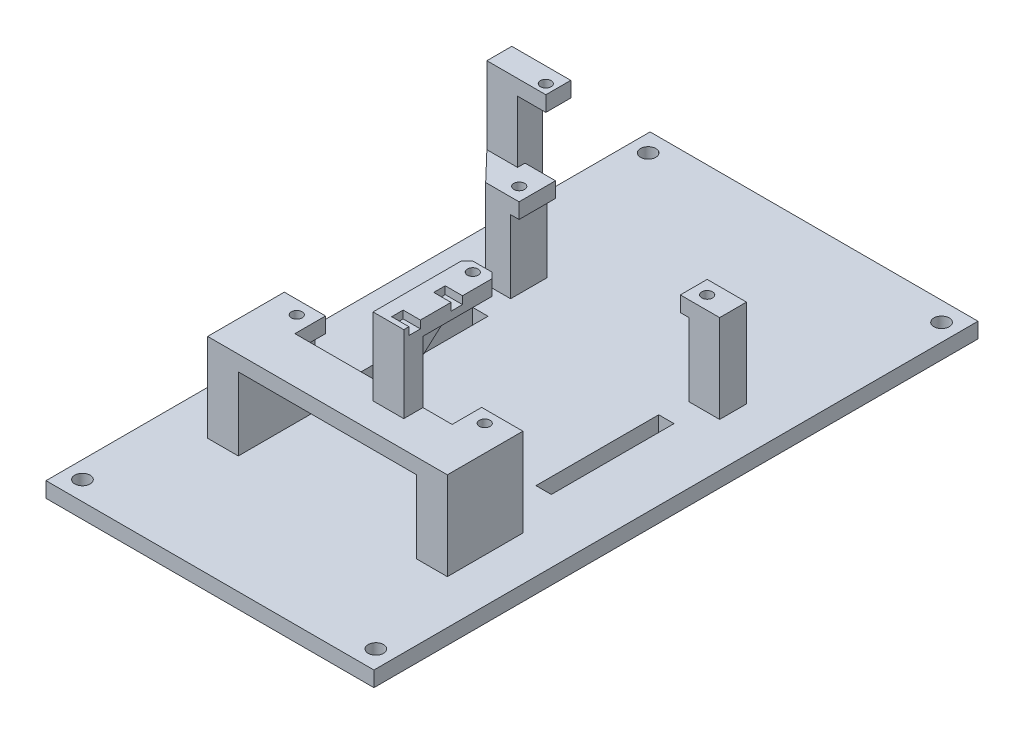
SolidWorks part; units mm, degrees
ref_plane "Front Plane" through (0, 0, 0) normal (0, 0, 1) x (1, 0, 0)
ref_plane "Top Plane" through (0, 0, 0) normal (0, 1, 0) x (1, 0, 0)
ref_plane "Right Plane" through (0, 0, 0) normal (1, 0, 0) x (0, 0, -1)
sketch "Sketch1" plane through (0, 0, 0) normal (0, 1, 0) x (1, 0, 0)
  line L1 (-42.75, 78.75) -> (42.75, 78.75)
  line L2 (-42.75, 78.75) -> (-42.75, -78.75)
  line L3 (-42.75, -78.75) -> (42.75, -78.75)
  line L4 (42.75, 78.75) -> (42.75, -78.75)
  line L5 (-42.75, 78.75) -> (42.75, -78.75) construction
  line L6 (-42.75, -78.75) -> (42.75, 78.75) construction
  point P0 (0, 0)
  dimension "D1" = 157.5
  dimension "D2" = 85.5
extrude "Boss-Extrude1" add sketch "Sketch1" along normal blind 4
sketch "Sketch2" plane through (0, 4, 0) normal (0, 1, 0) x (1, 0, 0)
  line L0 (-42.75, -78.75) -> (42.75, -78.75) construction
  line L1 (42.75, -78.75) -> (42.75, 78.75) construction
  line L2 (0, 0) -> (50000, 0) construction
  line L3 (0, 0) -> (0, -50000) construction
  circle A0 centre (38.25, -73.75) radius 2
  circle A1 centre (38.25, 73.75) radius 2
  circle A2 centre (-38.25, -73.75) radius 2
  circle A3 centre (-38.25, 73.75) radius 2
  dimension "D1" = 4
  dimension "D2" = 5
  dimension "D3" = 4.5
extrude "Cut-Extrude1" cut sketch "Sketch2" against normal up to next
sketch "Sketch5" plane through (0, 4, 0) normal (0, 1, 0) x (1, 0, 0)
  line L0 (-24.5, 26.3886) -> (-24.5, -31.6114) construction
  line L1 (-24.5, -31.6114) -> (24.5, -31.6114) construction
  line L2 (24.5, -31.6114) -> (24.5, 26.3886) construction
  line L3 (24.5, 26.3886) -> (-24.5, 26.3886) construction
  line L4 (0, 49.8886) -> (0, -35.1114) construction
  line L5 (-22.25, 67.25) -> (22.25, 67.25) construction
  line L6 (-22.25, 67.25) -> (-22.25, -67.25) construction
  line L7 (-22.25, -67.25) -> (22.25, -67.25) construction
  line L8 (22.25, 67.25) -> (22.25, -67.25) construction
  line L9 (-22.25, 67.25) -> (22.25, -67.25) construction
  line L10 (-22.25, -67.25) -> (22.25, 67.25) construction
  line L11 (-28, 49.8886) -> (28, 49.8886) construction
  line L12 (-28, 49.8886) -> (-28, -35.1114) construction
  line L13 (-28, -35.1114) -> (28, -35.1114) construction
  line L14 (28, 49.8886) -> (28, -35.1114) construction
  line L15 (24.5, 26.3886) -> (23.25, 26.3886) construction
  line L16 (-37, 36.9499) -> (-29, 36.9499)
  line L18 (-29.75, 22.8886) -> (-23.25, 22.8886)
  line L19 (-23.25, 32.3886) -> (-23.25, 22.8886)
  line L20 (23.25, 29.8886) -> (31.25, 29.8886)
  line L21 (23.25, 29.8886) -> (23.25, 22.8886)
  line L22 (23.25, 22.8886) -> (31.25, 22.8886)
  line L23 (31.25, 29.8886) -> (31.25, 22.8886)
  line L24 (-23.25, -48.1114) -> (23.25, -48.1114) construction
  line L25 (-31.25, -28.1114) -> (-23.25, -28.1114)
  line L26 (-31.25, -28.1114) -> (-31.25, -48.1114)
  line L27 (-31.25, -48.1114) -> (-23.25, -48.1114)
  line L28 (-23.25, -28.1114) -> (-23.25, -48.1114)
  line L29 (23.25, -28.4114) -> (31.25, -28.4114)
  line L30 (23.25, -28.4114) -> (23.25, -48.1114)
  line L31 (23.25, -48.1114) -> (31.25, -48.1114)
  line L32 (31.25, -28.4114) -> (31.25, -48.1114)
  line L33 (22.25, -16) -> (26.25, -16)
  line L34 (-22.25, -16) -> (-26.25, -16)
  line L35 (-22.25, -16) -> (-22.25, 16)
  line L36 (-22.25, 16) -> (-26.25, 16)
  line L37 (-26.25, -16) -> (-26.25, 16)
  line L38 (22.25, -16) -> (22.25, 16)
  line L39 (26.25, -16) -> (26.25, 16)
  line L40 (22.25, 16) -> (26.25, 16)
  line L41 (-23.25, 32.3886) -> (-29, 32.3886)
  line L42 (-29, 32.3886) -> (-29, 36.9499)
  line L43 (-37, 36.9499) -> (-37, 30.4499)
  line L44 (-37, 30.4499) -> (-29.75, 22.8886)
  circle A0 centre (-24.5, 26.3886) radius 1.4
  circle A1 centre (-24.13, 32.9499) radius 1.4
  circle A2 centre (8.89, -19.1201) radius 1.4
  circle A3 centre (24.5, -31.6114) radius 1.4
  circle A4 centre (24.5, 26.3886) radius 1.4
  circle A5 centre (-24.5, -31.6114) radius 1.4
  point P9 (0, 0)
  point P32 (23.25, 26.3886)
  point P46 (-22.25, 0)
  dimension "D1" = 24.5
  dimension "D2" = 26.3886
  dimension "D3" = 32.9499
  dimension "D4" = 24.13
  dimension "D5" = 2.8
  dimension "D6" = 33.02
  dimension "D7" = 52.07
  dimension "D8" = 49
  dimension "D9" = 58
  dimension "D18" = 4
  dimension "D21" = 3.5
  dimension "D24" = 3.5
  dimension "D10" = 44.5
  dimension "D11" = 134.5
  dimension "D12" = 56
  dimension "D13" = 85
  dimension "D14" = 28
  dimension "D15" = 3.5
  dimension "D16" = 1
  dimension "D17" = 3.5
  dimension "D19" = 6.5
  dimension "D20" = 1
  dimension "D22" = 8
  dimension "D23" = 1
  dimension "D25" = 1
  dimension "D26" = 3.2
  dimension "D27" = 8
  dimension "D28" = 8
  dimension "D29" = 20
  dimension "D30" = 32
  dimension "D31" = 4
  dimension "D32" = 6
  dimension "D33" = 1
  dimension "D34" = 8
  dimension "D35" = 6.5
extrude "Cut-Extrude3" cut sketch "Sketch5" against normal up to next contours L37 L34 L35 L36 | L39 L40 L38 L33 region at (-24.25, 4, 0)
extrude "Boss-Extrude3" add sketch "Sketch5<3>" along normal blind 23 contours L32 L29 L30 L31 | L28 L25 L26 L27 | L23 L20 L21 L22 | L43 L44 L18 L19 L41 L42 L16 | L28 A5 | L30 A3 | L21 A4 | L19 A0 | L41 A1 L19 region at (-30.3132, 4, -30.0503) region at (-24.2191, 4, -32.0291) region at (-24.5277, 4, -26.3886) region at (27.5785, 4, -26.3886) region at (24.5277, 4, -26.3886) region at (-27.3566, 4, 38.366) region at (-24.5277, 4, 31.6114) region at (27.3583, 4, 38.526) region at (24.5277, 4, 31.6114)
sketch "Sketch5<3>" plane through (0, 4, 0) normal (0, 1, 0) x (1, 0, 0) same geometry as "Sketch5"
sketch "Sketch6" plane through (-23.25, 0, 0) normal (1, 0, 0) x (0, 0, -1)
  line L0 (-28.1114, 27) -> (-28.1114, 4) construction
  line L1 (-48.1114, 27) -> (-28.1114, 27)
  line L2 (-48.1114, 27) -> (-48.1114, 23)
  line L3 (-48.1114, 23) -> (-28.1114, 23)
  line L4 (-28.1114, 27) -> (-28.1114, 23)
  line L5 (-28.1114, 4) -> (-48.1114, 4) construction
  dimension "D1" = 19
extrude "Boss-Extrude5" add sketch "Sketch6" along normal up to surface (46.5 mm away) up to face at (23.25, 15.5, 38.2614)
sketch "Sketch7" plane through (0, 27, 0) normal (0, 1, 0) x (1, 0, 0)
  line L0 (-31.25, -28.1114) -> (23.25, -28.1114) construction
  line L1 (-20.5, -28.1114) -> (23.25, -28.1114)
  line L2 (-20.5, -28.1114) -> (-20.5, -36.1114)
  line L3 (-20.5, -36.1114) -> (20.5, -36.1114)
  line L4 (20.5, -28.4114) -> (20.5, -36.1114)
  line L5 (23.25, -28.4114) -> (20.5, -28.4114)
  line L6 (23.25, -28.1114) -> (23.25, -28.4114)
  line L7 (-31.25, -28.1114) -> (-31.25, -48.1114) construction
  line L8 (31.25, -28.4114) -> (31.25, -48.1114) construction
  dimension "D1" = 10.75
  dimension "D2" = 10.75
  dimension "D3" = 8
extrude "Cut-Extrude4" cut sketch "Sketch7" against normal up to next
sketch "Sketch8" plane through (23.25, 0, 0) normal (-1, 0, 0) x (0, 0, 1)
  line L0 (-22.8886, 27) -> (-22.8886, 4) construction
  line L1 (-29.8886, 27) -> (-22.8886, 27)
  line L2 (-29.8886, 27) -> (-29.8886, 23)
  line L3 (-29.8886, 23) -> (-22.8886, 23)
  line L4 (-22.8886, 27) -> (-22.8886, 23)
  line L5 (-29.8886, 4) -> (-22.8886, 4) construction
  dimension "D1" = 19
extrude "Boss-Extrude6" add sketch "Sketch8" along normal blind 2.25
sketch "Sketch9" plane through (-23.25, 0, 0) normal (1, 0, 0) x (0, 0, -1)
  line L0 (32.3886, 27) -> (32.3886, 4) construction
  line L1 (22.8886, 27) -> (32.3886, 27)
  line L2 (22.8886, 27) -> (22.8886, 23)
  line L3 (22.8886, 23) -> (32.3886, 23)
  line L4 (32.3886, 27) -> (32.3886, 23)
  line L5 (32.3886, 4) -> (22.8886, 4) construction
  dimension "D1" = 19
extrude "Boss-Extrude7" add sketch "Sketch9" along normal blind 2.2
extrude "Cut-Extrude5" cut sketch "Sketch5<5>" against normal blind 3.5 from surface contours A0 | A4 | A3 | A5 starting at face at (0, 27, 35.1864)
sketch "Sketch5<5>" plane through (0, 4, 0) normal (0, 1, 0) x (1, 0, 0) same geometry as "Sketch5"
sketch "Sketch13" plane through (0, 27, 0) normal (0, 1, 0) x (1, 0, 0)
  line L0 (-29, 32.3886) -> (-29, 36.9499) construction
  line L1 (-37, 36.9499) -> (-29, 36.9499)
  line L2 (-37, 36.9499) -> (-37, 30.4499)
  line L3 (-37, 30.4499) -> (-29, 30.4499)
  line L4 (-29, 36.9499) -> (-29, 30.4499)
  line L5 (-20.5, -36.1114) -> (20.5, -36.1114) construction
  line L6 (4.89, -36.1114) -> (12.89, -36.1114)
  line L7 (4.89, -36.1114) -> (4.89, -41.1114)
  line L8 (4.89, -41.1114) -> (12.89, -41.1114)
  line L9 (12.89, -36.1114) -> (12.89, -41.1114)
  line L10 (8.89, -19.1201) -> (8.89, -36.1114) construction
  circle A0 centre (-24.13, 32.9499) radius 1.4 construction
  point P15 (8.89, -36.1114)
  dimension "D1" = 2.5
  dimension "D2" = 5
  dimension "D3" = 8
extrude "Boss-Extrude8" add sketch "Sketch13" along normal blind 20.1
sketch "Sketch14" plane through (-29, 0, 0) normal (1, 0, 0) x (0, 0, -1)
  line L0 (36.9499, 47.1) -> (36.9499, 4) construction
  line L1 (30.4499, 47.1) -> (36.9499, 47.1)
  line L2 (30.4499, 47.1) -> (30.4499, 43.1)
  line L3 (30.4499, 43.1) -> (36.9499, 43.1)
  line L4 (36.9499, 47.1) -> (36.9499, 43.1)
  dimension "D1" = 4
extrude "Boss-Extrude9" add sketch "Sketch14" along normal blind 7.37
sketch "Sketch15" plane through (0, 0, 36.1114) normal (0, 0, -1) x (-1, 0, 0)
  line L0 (-4.89, 47.1) -> (-4.89, 27) construction
  line L1 (-12.89, 47.1) -> (-4.89, 47.1)
  line L2 (-12.89, 47.1) -> (-12.89, 43.1)
  line L3 (-12.89, 43.1) -> (-4.89, 43.1)
  line L4 (-4.89, 47.1) -> (-4.89, 43.1)
  dimension "D1" = 4
extrude "Boss-Extrude10" add sketch "Sketch15" along normal blind 19.4913
extrude "Cut-Extrude6" cut sketch "Sketch5<6>" against normal up to next from surface contours A2 | A1 starting at face at (-29.315, 47.1, -33.6999)
sketch "Sketch5<6>" plane through (0, 4, 0) normal (0, 1, 0) x (1, 0, 0) same geometry as "Sketch5"
sketch "Sketch16" plane through (0, 47.1, 0) normal (0, 1, 0) x (1, 0, 0)
  line L0 (8.89, -19.1201) -> (8.89, -27.2991) construction
  line L1 (8.89, -27.2991) -> (12.89, -27.2991) construction
  line L2 (12.89, -41.1114) -> (12.89, -16.6201) construction
  line L3 (8.39, -28.7991) -> (12.89, -28.7991)
  line L4 (8.39, -25.7991) -> (8.39, -28.7991)
  line L5 (8.39, -25.7991) -> (12.89, -25.7991)
  line L6 (8.39, -39.7721) -> (12.89, -39.7721)
  line L7 (8.89, -28.2991) -> (12.89, -28.2991) construction
  line L8 (8.89, -26.2991) -> (12.89, -26.2991) construction
  line L10 (8.89, -26.2991) -> (8.89, -28.2991) construction
  line L11 (8.89, -27.2991) -> (8.89, -38.2721) construction
  line L12 (8.89, -38.2721) -> (12.89, -38.2721) construction
  line L13 (12.89, -41.1114) -> (12.89, -36.1114) construction
  line L14 (8.89, -39.2721) -> (12.89, -39.2721) construction
  line L15 (8.89, -37.2721) -> (12.89, -37.2721) construction
  line L16 (8.89, -37.2721) -> (8.89, -39.2721) construction
  line L18 (8.39, -36.7721) -> (8.39, -39.7721)
  line L19 (8.39, -36.7721) -> (12.89, -36.7721)
  line L20 (12.89, -25.7991) -> (12.89, -28.7991)
  line L21 (12.89, -36.7721) -> (12.89, -39.7721)
  dimension "D1" = 8.179
  dimension "D2" = 1
  dimension "D4" = 10.973
  dimension "D5" = 1
  dimension "D7" = 0.5
  dimension "D3" = 1
  dimension "D6" = 1
extrude "Cut-Extrude7" cut sketch "Sketch16" against normal blind 2
chamfer "Chamfer1" distance 1.5 angle 45 2 edges at (4.89, 45.1, 16.6201) (12.89, 45.1, 16.6201)
ref_plane "Plane1" through (8.89, 0, 0) normal (-1, 0, 0) x (0, 0, 1)
sketch "Sketch19" plane through (8.89, 0, 0) normal (-1, 0, 0) x (0, 0, 1)
  line L0 (27.1157, 43.1) -> (36.1114, 35.05)
  line L1 (18.1201, 43.1) -> (36.1114, 43.1) construction
  line L2 (36.1114, 43.1) -> (36.1114, 27) construction
  line L3 (27.1157, 43.1) -> (36.1114, 43.1)
  line L4 (36.1114, 43.1) -> (36.1114, 35.05)
extrude "Boss-Extrude11" add sketch "Sketch19" along normal blind 2 and the other way blind 2
sketch "Sketch20" plane through (0, 0, -36.9499) normal (0, 0, -1) x (-1, 0, 0)
  line L1 (37, 4) -> (31.25, 4)
  line L2 (37, 4) -> (37, 10)
  line L3 (37, 10) -> (31.25, 10)
  line L4 (31.25, 4) -> (31.25, 10)
  dimension "D1" = 5.75
  dimension "D2" = 6
extrude "Cut-Extrude8" cut sketch "Sketch20" against normal up to next
chamfer "Chamfer2" distance 5.75 angle 45 1 edges at (-37, 10, -33.6999)
sketch "Sketch21" plane through (0, 0, -36.9499) normal (0, 0, -1) x (-1, 0, 0)
  line L1 (31.25, 10) -> (29, 10)
  line L2 (31.25, 10) -> (31.25, 4)
  line L3 (31.25, 4) -> (29, 4)
  line L4 (29, 10) -> (29, 4)
extrude "Cut-Extrude9" cut sketch "Sketch21" against normal up to surface (4.5613 mm away) up to face at (-24.4333, 18, -32.3886)
chamfer "Chamfer3" distance 5.75 distance2 4.5613 1 edges at (-30.125, 10, -36.9499) first distance on face at (-29.5014, 30.8786, -36.9499)
